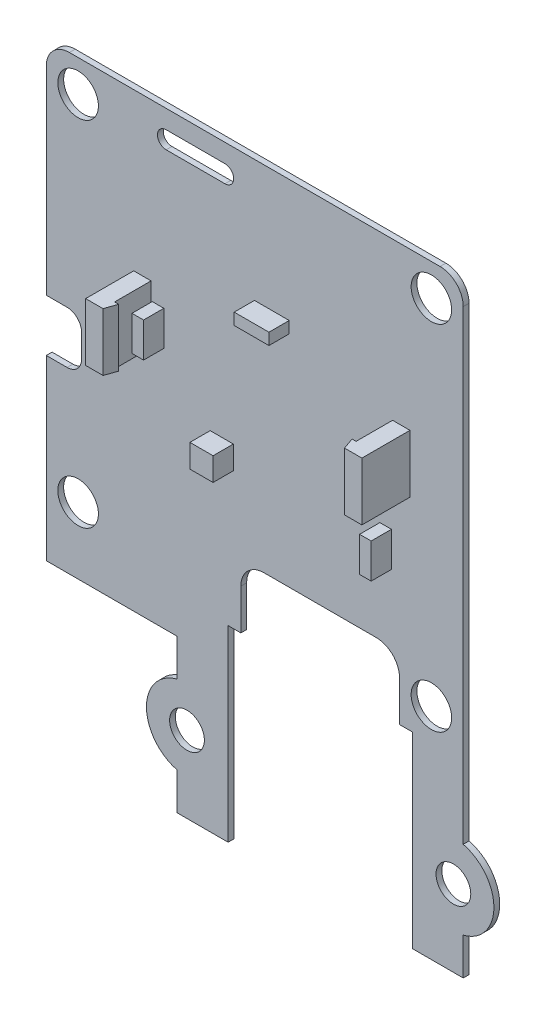
SolidWorks part; units mm, degrees
ref_plane "Front Plane" through (0, 0, 0) normal (0, 0, 1) x (1, 0, 0)
ref_plane "Top Plane" through (0, 0, 0) normal (0, 1, 0) x (1, 0, 0)
ref_plane "Right Plane" through (0, 0, 0) normal (1, 0, 0) x (0, 0, -1)
sketch "Sketch1" plane through (0, 0, 0) normal (0, 0, 1) x (1, 0, 0)
  line L1 (-14.95, -2.4) -> (-14.95, -4.4) construction
  line L2 (-16.2, -1.15) -> (-16.2, -5.65)
  line L3 (-14.95, -2.4) -> (-14.95, -4.4)
  line L4 (-7.65, 14.9) -> (-2.57, 14.9) construction
  line L5 (13.6, -18.1) -> (13.6, -34.2)
  line L6 (13.6, -34.2) -> (18, -34.2)
  line L7 (-2.3, -34.2) -> (-2.3, -18.1)
  line L8 (16, 18) -> (-16, 18)
  line L9 (-18, 16) -> (-18, -1.15)
  line L10 (-18, -18) -> (-1.2, -18)
  line L11 (-1.2, -18) -> (-1.2, -14.5)
  line L12 (0.8, -12.5) -> (10.5, -12.5)
  line L13 (12.5, -14.5) -> (12.5, -18)
  line L14 (12.5, -18) -> (18, -18)
  line L15 (18, -18) -> (18, 16)
  line L16 (16, 18) -> (-16, 18)
  line L17 (-18, 16) -> (-18, -1.15)
  line L18 (-18, -18) -> (-1.2, -18)
  line L19 (-1.2, -18) -> (-1.2, -14.5)
  line L20 (0.8, -12.5) -> (10.5, -12.5)
  line L21 (12.5, -14.5) -> (12.5, -18)
  line L22 (12.5, -18) -> (18, -18)
  line L23 (18, -18) -> (18, 16)
  line L24 (-2.3, -18.1) -> (-18, -18.1)
  line L25 (-18, -18.1) -> (-18, -21)
  line L26 (-18, -21) -> (-6.7, -21)
  line L27 (-6.7, -21) -> (-6.7, -24.2048)
  line L28 (-6.7, -30.9952) -> (-6.7, -34.2)
  line L29 (-6.7, -34.2) -> (-2.3, -34.2)
  line L30 (-2.3, -34.2) -> (-2.3, -18.1)
  line L31 (-2.3, -18.1) -> (-18, -18.1)
  line L32 (-18, -18.1) -> (-18, -21)
  line L33 (-18, -21) -> (-6.7, -21)
  line L34 (-6.7, -21) -> (-6.7, -24.2048)
  line L35 (-6.7, -30.9952) -> (-6.7, -34.2)
  line L36 (-6.7, -34.2) -> (-2.3, -34.2)
  line L37 (18, -34.2) -> (18, -30.9952)
  line L38 (18, -24.2048) -> (18, -18.1)
  line L39 (18, -18.1) -> (13.6, -18.1)
  line L40 (13.6, -18.1) -> (13.6, -34.2)
  line L41 (13.6, -34.2) -> (18, -34.2)
  line L42 (18, -34.2) -> (18, -30.9952)
  line L43 (18, -24.2048) -> (18, -18.1)
  line L44 (18, -18.1) -> (13.6, -18.1)
  line L45 (-7.65, 16.4) -> (-2.57, 16.4) construction
  line L46 (-7.65, 14.9) -> (-2.57, 14.9)
  line L47 (-7.65, 16.4) -> (-2.57, 16.4)
  line L48 (-18, -1.15) -> (-18, -18.1)
  line L49 (18, -18) -> (18, -18.1)
  line L50 (13.6, -18.1) -> (13.6, -18)
  line L51 (-2.3, -18.1) -> (-2.3, -18)
  line L112 (-18, -1.15) -> (-16.2, -1.15)
  line L113 (-18, -1.15) -> (-16.2, -1.15)
  line L114 (-14.95, -2.4) -> (-14.95, -4.4)
  line L115 (-14.95, -2.4) -> (-14.95, -4.4)
  line L116 (-16.2, -5.65) -> (-18, -5.65)
  line L117 (-16.2, -5.65) -> (-18, -5.65)
  line L118 (-18, -5.65) -> (-18, -18)
  line L119 (-18, -5.65) -> (-18, -18)
  arc A0 (-16.2, -5.65) -> (-14.95, -4.4) centre (-16.2, -4.4) ccw construction
  arc A1 (-6.7, -24.2048) -> (-6.7, -30.9952) centre (-5.85, -27.6) ccw
  arc A2 (-6.7, -24.2048) -> (-6.7, -30.9952) centre (-5.85, -27.6) ccw
  arc A3 (18, -30.9952) -> (18, -24.2048) centre (17.15, -27.6) ccw
  arc A4 (-16, 18) -> (-18, 16) centre (-16, 16) ccw
  arc A5 (0.8, -12.5) -> (-1.2, -14.5) centre (0.8, -14.5) ccw
  arc A6 (12.5, -14.5) -> (10.5, -12.5) centre (10.5, -14.5) ccw
  arc A7 (18, 16) -> (16, 18) centre (16, 16) ccw
  arc A8 (-16, 18) -> (-18, 16) centre (-16, 16) ccw
  arc A9 (0.8, -12.5) -> (-1.2, -14.5) centre (0.8, -14.5) ccw
  arc A10 (12.5, -14.5) -> (10.5, -12.5) centre (10.5, -14.5) ccw
  arc A11 (18, 16) -> (16, 18) centre (16, 16) ccw
  arc A12 (18, -30.9952) -> (18, -24.2048) centre (17.15, -27.6) ccw
  arc A13 (-14.95, -2.4) -> (-16.2, -1.15) centre (-16.2, -2.4) ccw construction
  arc A14 (-16.2, -5.65) -> (-14.95, -4.4) centre (-16.2, -4.4) ccw
  arc A15 (-14.95, -2.4) -> (-16.2, -1.15) centre (-16.2, -2.4) ccw
  circle A18 centre (17.15, -27.6) radius 1.5 construction
  circle A19 centre (-5.85, -27.6) radius 1.5 construction
  circle A22 centre (15.25, 15.25) radius 1.75
  circle A23 centre (15.25, -15.25) radius 1.75
  circle A24 centre (17.15, -27.6) radius 1.5
  circle A25 centre (-5.85, -27.6) radius 1.5
  circle A26 centre (-15.25, -15.25) radius 1.75
  circle A27 centre (-15.25, 15.25) radius 1.75
  arc A28 (-2.57, 14.9) -> (-2.57, 16.4) centre (-2.57, 15.65) ccw construction
  arc A29 (-7.65, 16.4) -> (-7.65, 14.9) centre (-7.65, 15.65) ccw construction
  arc A30 (-2.57, 14.9) -> (-2.57, 16.4) centre (-2.57, 15.65) ccw
  arc A31 (-7.65, 16.4) -> (-7.65, 14.9) centre (-7.65, 15.65) ccw
  circle A46 centre (15.25, -15.25) radius 1.75 construction
  circle A47 centre (-15.25, -15.25) radius 1.75 construction
  circle A48 centre (-15.25, 15.25) radius 1.75 construction
  circle A49 centre (15.25, 15.25) radius 1.75 construction
  arc A62 (-14.95, -2.4) -> (-16.2, -1.15) centre (-16.2, -2.4) ccw
  arc A63 (-14.95, -2.4) -> (-16.2, -1.15) centre (-16.2, -2.4) ccw
  arc A64 (-16.2, -5.65) -> (-14.95, -4.4) centre (-16.2, -4.4) ccw
  arc A65 (-16.2, -5.65) -> (-14.95, -4.4) centre (-16.2, -4.4) ccw
  dimension "D1" = 0
  dimension "D2" = 0
  dimension "D3" = 0
extrude "Base shape" add sketch "Sketch1" along normal blind 0.5 contours L23 A11 L16 A8 L17 L18 L19 A9 L20 A10 L21 L22 A31 L47 A30 L46 A27 A26 A23 A22 A15 L3 A14 L2 | L31 L51 L18 L48 | L34 A2 L35 L36 L30 L31 L32 L33 A25 | L50 L44 L49 L22 | L42 A12 L43 L44 L40 L41 A24 region at (-0.1312, 0.8573, 0) region at (-10.15, -18.05, 0) region at (-10.15, -18.3249, 0) region at (15.8, -18.05, 0) region at (16.2483, -26.2681, 0)
sketch "Sketch2" plane through (0, 0, 0.5) normal (0, 0, 1) x (1, 0, 0)
  line L0 (1.475, 16.95) -> (1.475, -13.05) construction
  line L1 (-7.85, 1.45) -> (-8.85, 1.45) construction
  line L2 (-0.025, 7.45) -> (2.975, 7.45)
  line L3 (-0.025, 7.45) -> (-0.025, 6.45)
  line L4 (11.8, 16.95) -> (-8.85, 16.95)
  line L5 (-8.85, 16.95) -> (-8.85, -13.05)
  line L6 (-8.85, -13.05) -> (11.8, -13.05)
  line L7 (11.8, -13.05) -> (11.8, 16.95)
  line L8 (11.8, 16.95) -> (-8.85, 16.95)
  line L9 (-8.85, 16.95) -> (-8.85, -13.05)
  line L10 (-8.85, -13.05) -> (11.8, -13.05)
  line L11 (11.8, -13.05) -> (11.8, 16.95)
  line L12 (-0.025, 6.45) -> (2.975, 6.45)
  line L13 (2.975, 7.45) -> (2.975, 6.45)
  line L14 (-0.025, 7.45) -> (2.975, 6.45) construction
  line L15 (-0.025, 6.45) -> (2.975, 7.45) construction
  line L16 (-8.85, 2.95) -> (-7.85, 2.95)
  line L17 (-8.85, 2.95) -> (-8.85, -0.05)
  line L18 (-8.85, -0.05) -> (-7.85, -0.05)
  line L19 (-7.85, 2.95) -> (-7.85, -0.05)
  line L20 (-3.85, -4.2) -> (-1.85, -4.2)
  line L21 (-3.85, -4.2) -> (-3.85, -6.2)
  line L22 (-3.85, -6.2) -> (-1.85, -6.2)
  line L23 (-1.85, -4.2) -> (-1.85, -6.2)
  line L24 (11.8, -3.75) -> (10.8, -3.75)
  line L25 (11.8, -3.75) -> (11.8, -6.75)
  line L26 (11.8, -6.75) -> (10.8, -6.75)
  line L27 (10.8, -3.75) -> (10.8, -6.75)
  line L28 (11.8, 1.95) -> (10.8, 1.95)
  line L29 (11.8, 1.95) -> (11.8, -1.05)
  line L30 (11.8, -1.05) -> (10.8, -1.05)
  line L31 (10.8, 1.95) -> (10.8, -1.05)
  line L32 (-3.85, -5.2) -> (-1.85, -5.2) construction
  line L33 (-2.85, -4.2) -> (-2.85, -6.2) construction
  line L34 (10.8, 0.45) -> (11.8, 0.45) construction
  line L35 (10.8, -5.25) -> (11.8, -5.25) construction
  point P6 (1.475, 6.95)
  dimension "D2" = 3
  dimension "D3" = 1
  dimension "D4" = 10
  dimension "D5" = 7.8
  dimension "D6" = 16.5
  dimension "D7" = 7.85
  dimension "D8" = 6
  dimension "D9" = 2
  dimension "D10" = 15.5
  dimension "D1" = 0
extrude "RX supports" add sketch "Sketch2" along normal blind 1.75 contours L13 L2 L3 L12 | L19 L16 L9 L18 | L23 L20 L21 L22 | L28 L31 L30 L11 | L24 L27 L26 L11 region at (1.475, 6.95, 0.5) region at (11.3, 0.45, 0.5) region at (-8.35, 1.45, 0.5) region at (11.3, -5.25, 0.5) region at (-2.85, -5.2, 0.5)
sketch "Sketch3" plane through (0, 0, 0.5) normal (0, 0, 1) x (1, 0, 0)
  line L0 (-8.85, 1.95) -> (11.8, 1.95) construction
  line L1 (1.475, 16.95) -> (1.475, -13.05) construction
  line L2 (-8.95, 4.45) -> (-10.45, 4.45)
  line L3 (-8.95, 4.45) -> (-8.95, -0.55)
  line L4 (11.8, 16.95) -> (-8.85, 16.95)
  line L5 (-8.85, 16.95) -> (-8.85, -13.05)
  line L6 (-8.85, -13.05) -> (11.8, -13.05)
  line L7 (11.8, -13.05) -> (11.8, 16.95)
  line L8 (11.8, 16.95) -> (-8.85, 16.95)
  line L9 (-8.85, 16.95) -> (-8.85, -13.05)
  line L10 (-8.85, -13.05) -> (11.8, -13.05)
  line L11 (11.8, -13.05) -> (11.8, 16.95)
  line L12 (-8.95, -0.55) -> (-10.45, -0.55)
  line L13 (-10.45, 4.45) -> (-10.45, -0.55)
  line L14 (11.9, -0.55) -> (13.4, -0.55)
  line L15 (13.4, 4.45) -> (13.4, -0.55)
  line L16 (11.9, 4.45) -> (13.4, 4.45)
  line L17 (11.9, 4.45) -> (11.9, -0.55)
  point P10 (-10.45, 1.95)
  point P13 (0, 0)
  point P14 (0, 0)
  point P15 (-9.1855, 4.45)
  dimension "D2" = 5
  dimension "D3" = 1.5
  dimension "D4" = 0.1
  dimension "D1" = 0
extrude "Clip base" add sketch "Sketch3" along normal offset from surface (3.15 mm away) 0.2 contours L2 L13 L12 L3 | L16 L17 L14 L15 region at (-9.7, 1.95, 0.5) region at (12.65, 1.95, 0.5) offset beyond the face yes
sketch "Sketch4" plane through (0, 0, 3.65) normal (0, 0, 1) x (1, 0, 0)
  line L0 (-8.95, -0.55) -> (-10.45, -0.55) construction
  line L1 (-10.45, 4.45) -> (-8.6, 4.45)
  line L2 (-10.45, 4.45) -> (-10.45, -0.55)
  line L3 (-10.45, -0.55) -> (-8.6, -0.55)
  line L4 (-8.6, 4.45) -> (-8.6, -0.55)
  line L5 (-8.95, 4.45) -> (-8.95, -0.55) construction
  line L6 (-10.45, 1.95) -> (13.4, 1.95) construction
  line L7 (13.4, 4.45) -> (13.4, -0.55) construction
  line L8 (1.475, 4.45) -> (1.475, -0.55) construction
  line L9 (11.55, 4.45) -> (11.55, -0.55)
  line L10 (13.4, 4.45) -> (11.55, 4.45)
  line L11 (13.4, 4.45) -> (13.4, -0.55)
  line L12 (13.4, -0.55) -> (11.55, -0.55)
  point P15 (0, 0)
  point P16 (0, 0)
  point P17 (1.475, 1.95)
  dimension "D1" = 0.35
extrude "Clip top" add sketch "Sketch4" along normal blind 1
sketch "Sketch5" plane through (0, -0.55, 0) normal (0, -1, 0) x (1, 0, 0)
  line L0 (-8.6, 3.65) -> (-8.95, 4.65)
  line L1 (-10.45, 4.65) -> (-8.6, 4.65) construction
  line L2 (-8.95, 4.65) -> (-8.6, 4.65)
  line L3 (-8.6, 4.65) -> (-8.6, 3.65)
  line L4 (-8.95, 3.65) -> (-8.95, 0.5) construction
  line L5 (11.55, 3.65) -> (11.9, 4.65)
  line L6 (11.55, 4.65) -> (13.4, 4.65) construction
  line L7 (11.9, 4.65) -> (11.55, 4.65)
  line L8 (11.55, 4.65) -> (11.55, 3.65)
  line L9 (11.9, 3.65) -> (11.9, 0.5) construction
  point P5 (0, 0)
extrude "Clip chamfer" cut sketch "Sketch5" against normal up to next
